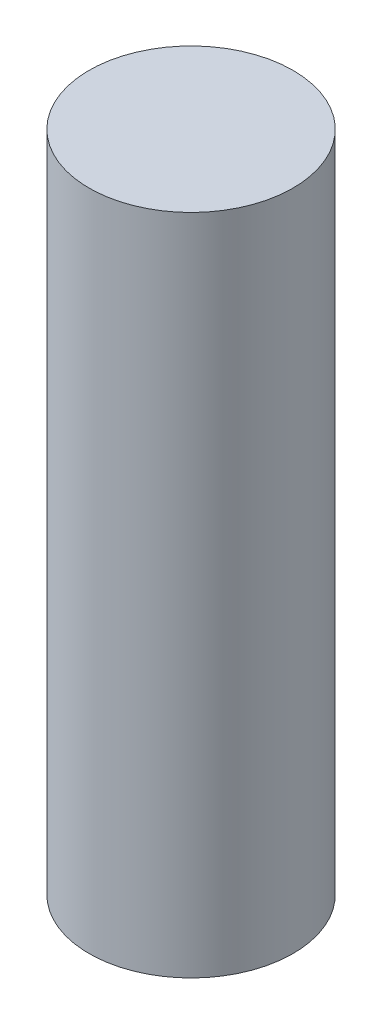
SolidWorks part; units mm, degrees
ref_plane "Front Plane" through (0, 0, 0) normal (0, 0, 1) x (1, 0, 0)
ref_plane "Top Plane" through (0, 0, 0) normal (0, 1, 0) x (1, 0, 0)
ref_plane "Right Plane" through (0, 0, 0) normal (1, 0, 0) x (0, 0, -1)
sketch "Sketch1" plane through (0, 0, 0) normal (0, 1, 0) x (1, 0, 0)
  circle A0 centre (0, 0) radius 4
  dimension "D1" = 8
extrude "Boss-Extrude1" add sketch "Sketch1" along normal blind 26
